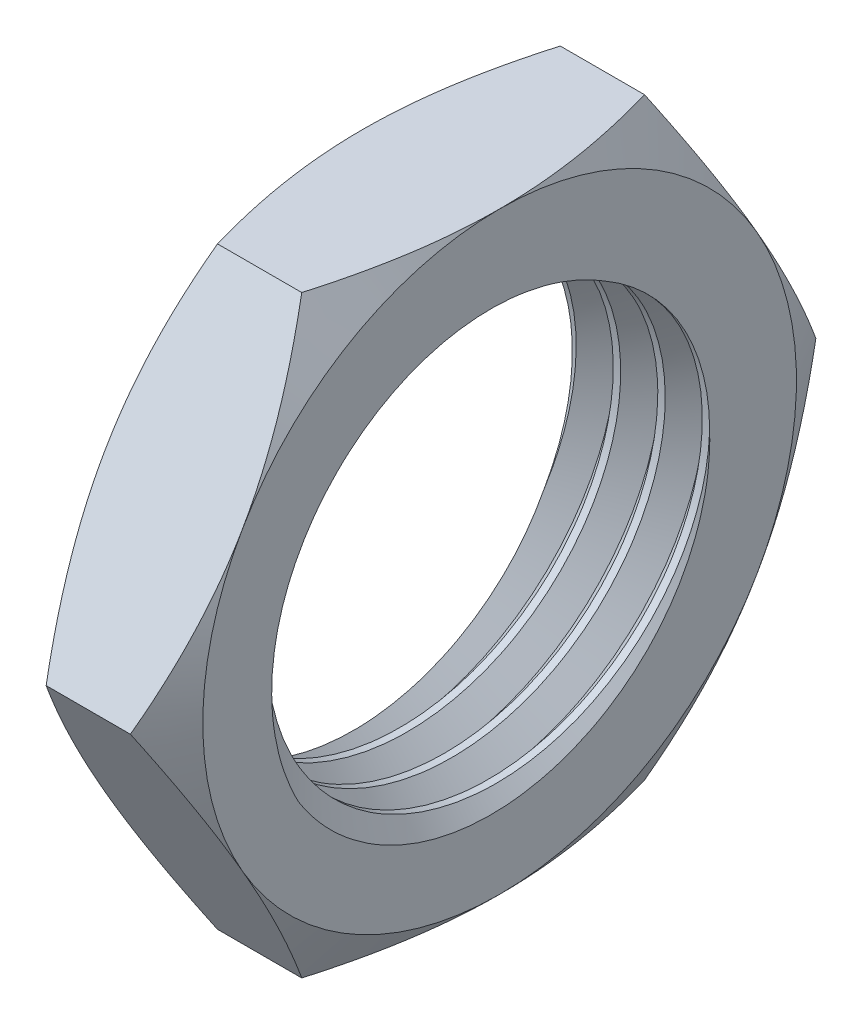
SolidWorks part; units mm, degrees
material "Brass"
ref_plane "Front Plane" through (0, 0, 0) normal (0, 0, 1) x (1, 0, 0)
ref_plane "Top Plane" through (0, 0, 0) normal (0, 1, 0) x (1, 0, 0)
ref_plane "Right Plane" through (0, 0, 0) normal (1, 0, 0) x (0, 0, -1)
sketch "Sketch1" plane through (0, 0, 0) normal (1, 0, 0) x (0, 0, -1)
  line L1 (4.6188, 0) -> (2.3094, 4)
  line L2 (2.3094, 4) -> (-2.3094, 4)
  line L3 (-2.3094, 4) -> (-4.6188, 0)
  line L4 (-4.6188, 0) -> (-2.3094, -4)
  line L5 (-2.3094, -4) -> (2.3094, -4)
  line L6 (2.3094, -4) -> (4.6188, 0)
  circle A0 centre (0, 0) radius 4 construction
  dimension "D1" = 8
extrude "Boss-Extrude1" add sketch "Sketch1" along normal blind 1.85
sketch "Sketch2" plane through (0, 0, 0) normal (0, 0, 1) x (1, 0, 0)
  line L0 (-0.3297, 3.4289) -> (-0.3297, 5.4289)
  line L1 (-0.3297, 5.4289) -> (0.825, 5.4289)
  line L2 (0.825, 5.4289) -> (-0.3297, 3.4289)
  line L3 (0.925, 4) -> (0.925, 0) construction
  line L4 (1.85, 4) -> (0, 4) construction
  line L5 (1.85, 0) -> (0, 0) construction
  line L6 (1.025, 5.4289) -> (2.1797, 3.4289)
  line L7 (2.1797, 5.4289) -> (1.025, 5.4289)
  line L8 (2.1797, 3.4289) -> (2.1797, 5.4289)
  line L9 (0, 0) -> (1.85, 0) construction
  dimension "D1" = 30
  dimension "D2" = 0.2
  dimension "D3" = 2
revolve "Cut-Revolve1" cut sketch "Sketch2" angle 360 about L9
sketch "Sketch3" plane through (1.85, 0, 0) normal (1, 0, 0) x (0, 0, -1)
  circle A0 centre (0, 0) radius 2.83
  dimension "D1" = 5.66
extrude "Cut-Extrude1" cut sketch "Sketch3" against normal through all
sketch "Sketch4" plane through (1.85, 0, 0) normal (1, 0, 0) x (0, 0, -1)
  circle A1 centre (0, 0) radius 2.83
  circle A2 centre (0, 0) radius 2.83
  dimension "D1" = 0
curve "Helix/Spiral1" pitch 0.6 height 3 turns 5
sketch "Sketch5" plane through (0, 0, 0) normal (0, 1, 0) x (1, 0, 0)
  line L0 (1.85, 2.83) -> (2.1, 3.13)
  line L1 (2.1, 3.13) -> (2.35, 2.83)
  line L2 (2.35, 2.83) -> (1.85, 2.83)
  line L3 (2.1, 2.83) -> (2.1, 3.13) construction
  dimension "D1" = 0.5
  dimension "D2" = 0.3
sweep "Cut-Sweep1" cut profiles "Sketch5" path "Helix/Spiral1" align with end faces yes
equation "\"panjang\"= 120"
equation "\"lebar\"=40"
equation "\"tinggi\"=10"
